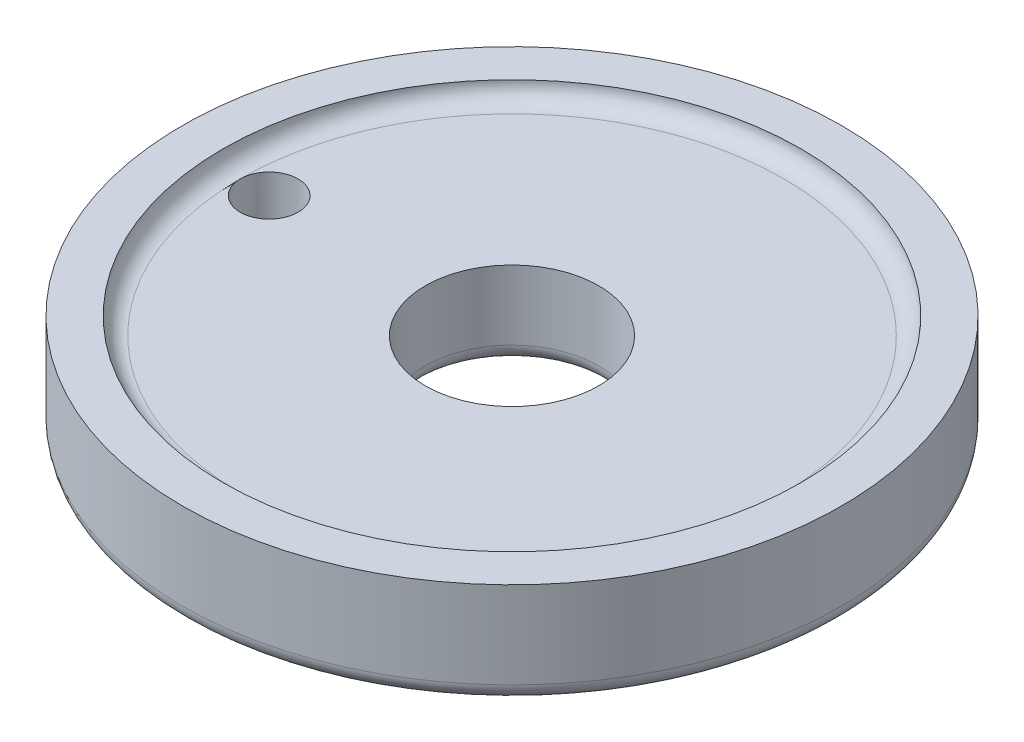
SolidWorks part; units mm, degrees
ref_plane "Front Plane" through (0, 0, 0) normal (0, 0, 1) x (1, 0, 0)
ref_plane "Top Plane" through (0, 0, 0) normal (0, 1, 0) x (1, 0, 0)
ref_plane "Right Plane" through (0, 0, 0) normal (1, 0, 0) x (0, 0, -1)
sketch "Sketch1" plane through (0, 0, 0) normal (0, 1, 0) x (1, 0, 0)
  circle A0 centre (0, 0) radius 15
  circle A1 centre (0, 0) radius 42 construction
  circle A2 centre (0, 0) radius 57
  circle A3 centre (-42, 0) radius 5
  dimension "D1" = 114
  dimension "D2" = 84
  dimension "D3" = 30
  dimension "D4" = 10
extrude "Boss-Extrude1" add sketch "Sketch1" against normal blind 18
cosmetic thread "Cosmetic Thread1" parameters "D2"=12
fillet "Fillet1" radius 3 2 edges at (0, -18, 57) (0, -18, 15)
sketch "Sketch2" plane through (0, 0, 0) normal (0, 1, 0) x (1, 0, 0)
  circle A0 centre (0, 0) radius 50
  circle A1 centre (0, 0) radius 15
  dimension "D1" = 100
  dimension "D2" = 30
extrude "Cut-Extrude1" cut sketch "Sketch2" against normal blind 3
fillet "Fillet2" radius 3 1 edges at (0, -3, 50)
